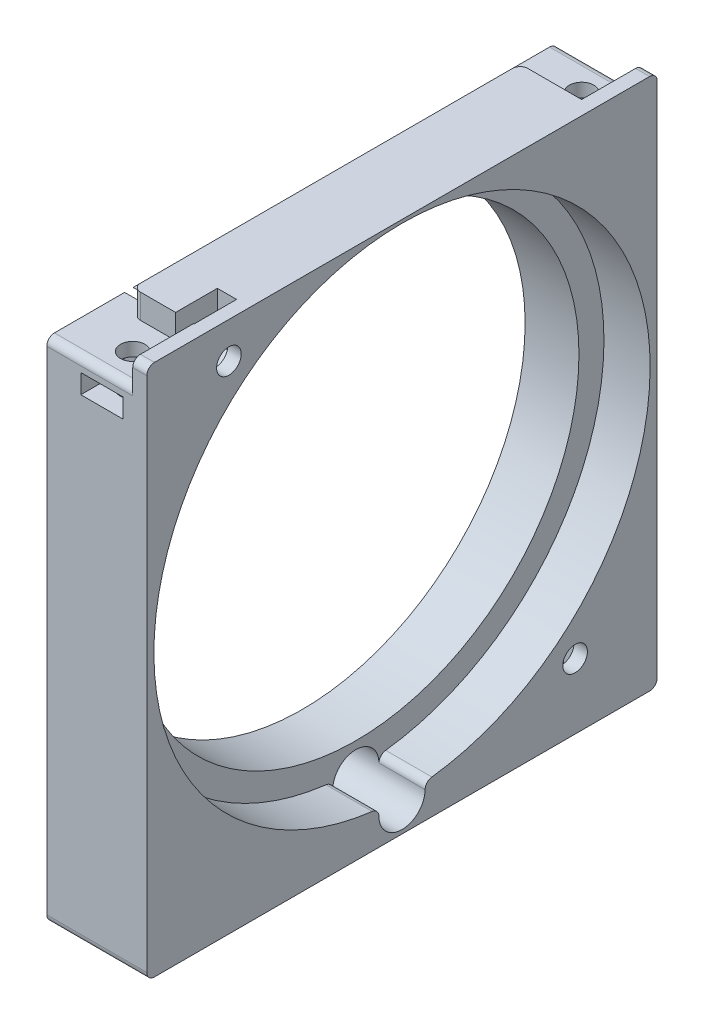
SolidWorks part; units mm, degrees
ref_plane "Front Plane" through (0, 0, 0) normal (0, 0, 1) x (1, 0, 0)
ref_plane "Top Plane" through (0, 0, 0) normal (0, 1, 0) x (1, 0, 0)
ref_plane "Right Plane" through (0, 0, 0) normal (1, 0, 0) x (0, 0, -1)
sketch "Sketch1" plane through (0, 0, 0) normal (1, 0, 0) x (0, 0, -1)
  line L0 (0, -34.59) -> (0, -31.09) construction
  line L1 (-33.175, -34.59) -> (33.175, -34.59)
  line L2 (-33.175, -34.59) -> (-33.175, 34.59)
  line L3 (-33.175, 34.59) -> (33.175, 34.59)
  line L4 (33.175, -34.59) -> (33.175, 34.59)
  line L5 (-33.175, -34.59) -> (33.175, 34.59) construction
  line L6 (-33.175, 34.59) -> (33.175, -34.59) construction
  line L9 (-22.5, -26.09) -> (22.5, -26.09) construction
  line L10 (-22.5, -26.09) -> (-22.5, 29.91) construction
  line L11 (-22.5, 29.91) -> (22.5, 29.91) construction
  line L12 (22.5, -26.09) -> (22.5, 29.91) construction
  line L13 (-22.5, -26.09) -> (22.5, 29.91) construction
  line L14 (-22.5, 29.91) -> (22.5, -26.09) construction
  circle A1 centre (0, 1.91) radius 29
  point P0 (0, 0)
  point P10 (0, -34.59)
  dimension "D1" = 36.5
  dimension "D2" = 58
  dimension "D5" = 3.5
  dimension "D3" = 69.18
  dimension "D4" = 66.35
  dimension "D6" = 28
  dimension "D8" = 33
  dimension "D9" = 45
extrude "Boss-Extrude1" add sketch "Sketch1" along normal blind 7
sketch "Sketch3" plane through (7, 0, 0) normal (1, 0, 0) x (0, 0, -1)
  line L4 (33.175, -34.59) -> (33.175, 34.59)
  line L5 (33.175, 34.59) -> (-33.175, 34.59)
  line L6 (-33.175, 34.59) -> (-33.175, -34.59)
  line L7 (-33.175, -34.59) -> (33.175, -34.59)
  line L8 (33.175, -34.59) -> (33.175, 34.59)
  line L9 (33.175, 34.59) -> (-33.175, 34.59)
  line L10 (-33.175, 34.59) -> (-33.175, -34.59)
  line L11 (-33.175, -34.59) -> (33.175, -34.59)
  circle A0 centre (0, 1.91) radius 32.25
  dimension "D1" = 64.5
  dimension "D2" = 0
extrude "Boss-Extrude2" add sketch "Sketch3" along normal blind 6
sketch "Sketch5" plane through (0, 34.59, 0) normal (0, 1, 0) x (1, 0, 0)
  line L0 (3.175, 33.175) -> (11.175, 25.175) construction
  line L1 (3.175, 33.175) -> (11.175, 33.175)
  line L2 (3.175, 33.175) -> (3.175, 25.175) construction
  line L3 (3.175, 25.175) -> (11.175, 25.175)
  line L4 (11.175, 33.175) -> (11.175, 25.175)
  line L5 (3.175, -33.175) -> (11.175, -33.175)
  line L6 (3.175, -33.175) -> (3.175, -25.175) construction
  line L7 (3.175, -25.175) -> (11.175, -25.175)
  line L8 (11.175, -33.175) -> (11.175, -25.175)
  line L9 (11.175, -25.175) -> (3.175, -33.175) construction
  line L11 (13, -33.175) -> (0, -33.175) construction
  line L13 (0, 33.175) -> (0, -33.175) construction
  line L15 (0, -33.175) -> (3.175, -33.175)
  line L16 (3.175, 33.175) -> (0, 33.175)
  line L17 (0, 33.175) -> (0, -33.175)
  line L19 (3.175, -25.175) -> (3.175, 25.175)
  line L20 (13, 33.175) -> (0, 33.175) construction
  circle A0 centre (7.175, 29.175) radius 2.5273 construction
  circle A1 centre (7.175, -29.175) radius 2.5273 construction
  dimension "D1" = 5.0546
  dimension "D2" = 4
  dimension "D3" = 3.175
  dimension "D4" = 4
extrude "Cut-Extrude1" cut sketch "Sketch5" against normal offset from surface (3.18 mm away) 66 up to face at (6.5, -34.59, 0)
ref_plane "Plane2" through (0, 28.41, 0) normal (0, 1, 0) x (1, 0, 0)
sketch "Sketch8" plane through (0, 28.41, 0) normal (0, 1, 0) x (1, 0, 0)
  line L0 (4.425, -30.7627) -> (4.425, -33.175)
  line L1 (7.175, 32.3504) -> (4.425, 30.7627) construction
  line L2 (4.425, 30.7627) -> (4.425, 27.5873)
  line L3 (4.425, 27.5873) -> (7.175, 25.9996)
  line L4 (7.175, 25.9996) -> (9.925, 27.5873)
  line L5 (9.925, 27.5873) -> (9.925, 30.7627)
  line L6 (9.925, 30.7627) -> (7.175, 32.3504) construction
  line L7 (7.175, -32.3504) -> (9.925, -30.7627) construction
  line L8 (9.925, -30.7627) -> (9.925, -27.5873)
  line L9 (9.925, -27.5873) -> (7.175, -25.9996)
  line L10 (7.175, -25.9996) -> (4.425, -27.5873)
  line L11 (4.425, -27.5873) -> (4.425, -30.7627)
  line L12 (4.425, -30.7627) -> (7.175, -32.3504) construction
  line L13 (11.175, -33.175) -> (0, -33.175) construction
  line L14 (4.425, -33.175) -> (9.925, -33.175)
  line L15 (9.925, -33.175) -> (9.925, -30.7627)
  line L16 (4.425, 30.7627) -> (4.425, 33.175)
  line L17 (0, 33.175) -> (11.175, 33.175) construction
  line L18 (4.425, 33.175) -> (9.925, 33.175)
  line L19 (9.925, 33.175) -> (9.925, 30.7627)
  circle A0 centre (7.175, 29.175) radius 2.5273 construction
  circle A1 centre (7.175, 29.175) radius 2.5273 construction
  circle A2 centre (7.175, -29.175) radius 2.5273 construction
  circle A3 centre (7.175, -29.175) radius 2.5273 construction
  circle A4 centre (7.175, 29.175) radius 2.75 construction
  circle A5 centre (7.175, -29.175) radius 2.75 construction
  dimension "D1" = 5.5
extrude "Cut-Extrude5" cut sketch "Sketch8" against normal mid plane 2.5
hole_wizard "M3 Clearance Hole3" positions "Sketch16" profile "Sketch17" hole size "M3" standard "ANSI Metric"
sketch "Sketch16" plane through (0, 31.41, 0) normal (0, 1, 0) x (1, 0, 0)
  point P0 (7.175, 29.175)
  point P3 (7.175, -29.175)
sketch "Sketch17" plane through (7.175, 31.41, -29.175) normal (1, 0, 0) x (0, 0, 1)
  line L0 (0, 0) -> (0, 10.9614)
  line L1 (0, 10.9614) -> (1.6, 10)
  line L2 (1.6, 10) -> (1.6, 0)
  line L5 (1.6, 0) -> (0, 0)
  line L10 (0, 10.9614) -> (-1.6, 10) construction
  line L11 (0, -6.35) -> (0, 107.95) construction
  dimension "Hole Dia." = 3.2
  dimension "Hole Depth" = 10
  dimension "Drill Angle" = 118
sketch "Sketch14" plane through (13, 0, 0) normal (1, 0, 0) x (0, 0, -1)
  circle A0 centre (0, -31.09) radius 3
  dimension "D1" = 6
extrude "Cut-Extrude3" cut sketch "Sketch14" against normal offset from surface (11 mm away) 5 up to face at (7, 1.91, -29) offset beyond the face yes
ref_plane "Plane1" through (10, 0, 0) normal (1, 0, 0) x (0, 0, -1)
sketch "Sketch15" plane through (10, 0, 0) normal (1, 0, 0) x (0, 0, -1)
  line L0 (19.75, -27.6777) -> (19.75, -34.59)
  line L1 (-22.5, 33.0854) -> (-25.25, 31.4977) construction
  line L2 (-25.25, 31.4977) -> (-25.25, 28.3223)
  line L3 (-25.25, 28.3223) -> (-22.5, 26.7346)
  line L4 (-22.5, 26.7346) -> (-19.75, 28.3223)
  line L5 (-19.75, 28.3223) -> (-19.75, 31.4977)
  line L6 (-19.75, 31.4977) -> (-22.5, 33.0854) construction
  line L7 (22.5, -29.2654) -> (25.25, -27.6777) construction
  line L8 (25.25, -27.6777) -> (25.25, -24.5023)
  line L9 (25.25, -24.5023) -> (22.5, -22.9146)
  line L10 (22.5, -22.9146) -> (19.75, -24.5023)
  line L11 (19.75, -24.5023) -> (19.75, -27.6777)
  line L12 (19.75, -27.6777) -> (22.5, -29.2654) construction
  line L13 (-33.175, -34.59) -> (33.175, -34.59) construction
  line L14 (19.75, -34.59) -> (25.25, -34.59)
  line L15 (25.25, -34.59) -> (25.25, -27.6777)
  line L16 (-25.25, 31.4977) -> (-25.25, 34.59)
  line L17 (33.175, 34.59) -> (-33.175, 34.59) construction
  line L18 (-25.25, 34.59) -> (-19.75, 34.59)
  line L19 (-19.75, 34.59) -> (-19.75, 31.4977)
  circle A0 centre (-22.5, 29.91) radius 2.5 construction
  circle A1 centre (22.5, 29.91) radius 2.5 construction
  circle A2 centre (-22.5, -26.09) radius 2.5 construction
  circle A4 centre (22.5, -26.09) radius 2.5 construction
  circle A5 centre (-22.5, 29.91) radius 2.75 construction
  circle A6 centre (22.5, -26.09) radius 2.75 construction
  dimension "D1" = 5
  dimension "D2" = 5.5
extrude "Cut-Extrude4" cut sketch "Sketch15" against normal mid plane 2.5
hole_wizard "M3 Clearance Hole2" positions "Sketch11" profile "Sketch13" hole size "M3" standard "ANSI Metric" end condition through all
sketch "Sketch11" plane through (13, 0, 0) normal (1, 0, 0) x (0, 0, -1)
  point P0 (0, -31.09)
  point P29 (-22.5, 29.91)
  point P32 (22.5, -26.09)
sketch "Sketch13" plane through (13, -31.09, 0) normal (0, 1, 0) x (0, 0, -1)
  line L0 (0, 0) -> (0, 13)
  line L1 (0, 13) -> (1.6, 13)
  line L2 (1.6, 13) -> (1.6, 0)
  line L5 (1.6, 0) -> (0, 0)
  line L11 (0, -6.35) -> (0, 107.95) construction
  dimension "Thru Hole Dia." = 3.2
  dimension "Thru Hole Depth" = 13
fillet "Fillet1" radius 1 10 edges at (3.175, 33, -25.175) (3.175, 33, 25.175) (5.5875, 31.41, -33.175) (5.5875, 31.41, 33.175) (10, -30.2122, 2.8687) (10, -30.2122, -2.8687) (6.5, -34.59, -33.175) (6.5, -34.59, 33.175) (12.0875, 34.59, -33.175) (12.0875, 34.59, 33.175)
